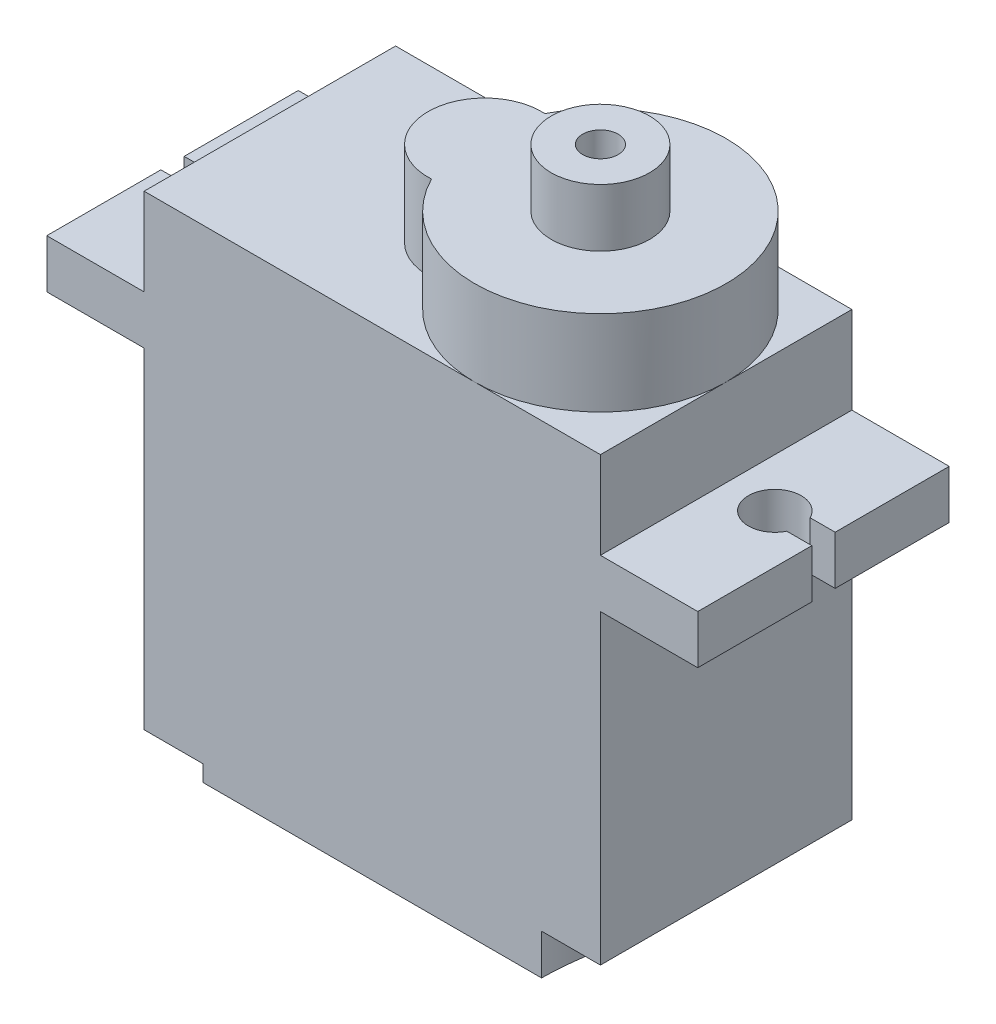
SolidWorks part; units mm, degrees
ref_plane "Alzado" through (0, 0, 0) normal (0, 0, 1) x (1, 0, 0)
ref_plane "Planta" through (0, 0, 0) normal (0, 1, 0) x (1, 0, 0)
ref_plane "Vista lateral" through (0, 0, 0) normal (1, 0, 0) x (0, 0, -1)
sketch "Croquis1" plane through (0, 0, 0) normal (0, 0, 1) x (1, 0, 0)
  line L0 (0, 11.9) -> (0, -11.9) construction
  line L4 (-11.25, -11.9) -> (-11.25, 11.9)
  line L5 (-11.25, 11.9) -> (11.25, 11.9)
  line L6 (-11.25, -11.9) -> (11.25, -11.9)
  line L7 (-16.05, 5.2) -> (-11.25, 5.2)
  line L8 (-16.05, 5.2) -> (-16.05, 7.6)
  line L9 (-16.05, 7.6) -> (-11.25, 7.6)
  line L10 (-11.25, 5.2) -> (-11.25, 7.6)
  line L11 (-16.05, 5.2) -> (-11.25, 7.6) construction
  line L12 (-16.05, 7.6) -> (-11.25, 5.2) construction
  line L14 (11.25, -11.9) -> (11.25, 11.9)
  line L16 (16.05, 7.6) -> (11.25, 7.6)
  line L17 (11.25, 5.2) -> (11.25, 7.6)
  line L18 (16.05, 5.2) -> (11.25, 5.2)
  line L19 (16.05, 5.2) -> (16.05, 7.6)
  point P0 (0, 0)
  point P2 (-11.25, 0)
  point P6 (-13.65, 6.4)
  dimension "D1" = 23.8
  dimension "D2" = 2.4
  dimension "D3" = 22.5
  dimension "D4" = 4.8
  dimension "D5" = 4.3
extrude "Saliente-Extruir1" add sketch "Croquis1" along normal mid plane 12.4 contours L9 L8 L7 L4 | L6 L14 L5 L4 | L18 L19 L16 L14 region at (0, 0, 0) region at (-13.65, 6.4, 0) region at (13.65, 6.4, 0)
sketch "Croquis2" plane through (0, 11.9, 0) normal (0, 1, 0) x (1, 0, 0)
  line L0 (-11.25, 6.2) -> (11.25, 6.2) construction
  line L1 (-11.25, -6.2) -> (11.25, -6.2) construction
  line L2 (11.25, -6.2) -> (11.25, 6.2) construction
  line L3 (-0.65, 0) -> (-3.45, 0) construction
  arc A0 (-0.4842, -2.7951) -> (-0.4842, 2.7951) centre (5.05, 0) ccw
  arc A1 (-0.4842, 2.7951) -> (-0.4842, -2.7951) centre (-0.65, 0) ccw
  dimension "D2" = 5.6
  dimension "D1" = 14.7
extrude "Saliente-Extruir2" add sketch "Croquis2" along normal blind 4.2
sketch "Croquis3" plane through (0, 7.6, 0) normal (0, 1, 0) x (1, 0, 0)
  line L0 (0, -6.2) -> (0, 6.2) construction
  line L1 (-11.25, -6.2) -> (5.05, -6.2) construction
  line L2 (-11.25, 6.2) -> (5.05, 6.2) construction
  line L3 (16.05, 0.575) -> (14.8159, 0.575)
  line L4 (16.05, -6.2) -> (16.05, 6.2) construction
  line L5 (16.05, -0.575) -> (14.8159, -0.575)
  line L6 (16.05, 0.575) -> (16.05, -0.575)
  line L7 (-16.05, 0.575) -> (-14.8159, 0.575)
  line L8 (-16.05, 0.575) -> (-16.05, -0.575)
  line L9 (-16.05, -0.575) -> (-14.8159, -0.575)
  arc A1 (14.8159, 0.575) -> (14.8159, -0.575) centre (13.65, 0) ccw
  arc A2 (-14.8159, 0.575) -> (-14.8159, -0.575) centre (-13.65, 0) cw
  point P16 (16.05, 0)
  point P18 (16.05, 0)
  dimension "D2" = 2.6
  dimension "D1" = 1.15
  dimension "D3" = 2.4
extrude "Cortar-Extruir1" cut sketch "Croquis3" against normal up to next
sketch "Croquis4" plane through (0, -11.9, 0) normal (0, -1, 0) x (1, 0, 0)
  line L0 (0, 6.2) -> (0, -6.2) construction
  line L1 (-11.25, 0) -> (11.25, 0) construction
  line L2 (-11.25, 3.3) -> (-11.25, 6.2)
  line L3 (-11.25, 6.2) -> (-8.35, 6.2)
  line L4 (-11.25, -6.2) -> (11.25, -6.2)
  line L5 (11.25, -6.2) -> (11.25, 6.2)
  line L6 (11.25, 6.2) -> (-11.25, 6.2)
  line L7 (-11.25, 6.2) -> (-11.25, -6.2)
  line L8 (-11.25, -6.2) -> (11.25, -6.2)
  line L9 (11.25, -6.2) -> (11.25, 6.2)
  line L10 (11.25, 6.2) -> (-11.25, 6.2)
  line L11 (-11.25, 6.2) -> (-11.25, -6.2)
  line L12 (-11.25, -3.3) -> (-11.25, -6.2)
  line L13 (-11.25, -6.2) -> (-8.35, -6.2)
  line L14 (11.25, 3.3) -> (11.25, 6.2)
  line L15 (11.25, 6.2) -> (8.35, 6.2)
  line L16 (11.25, -3.3) -> (11.25, -6.2)
  line L17 (11.25, -6.2) -> (8.35, -6.2)
  line L18 (8.35, 6.2) -> (8.35, -6.2)
  line L19 (9.75, -1.875) -> (11.25, -1.875)
  line L20 (9.75, -1.875) -> (9.75, 1.875)
  line L21 (9.75, 1.875) -> (11.25, 1.875)
  line L22 (11.25, -1.875) -> (11.25, 1.875)
  line L23 (9.75, -1.875) -> (11.25, 1.875) construction
  line L24 (9.75, 1.875) -> (11.25, -1.875) construction
  arc A0 (-8.35, 6.2) -> (-11.25, 3.3) centre (-11.25, 6.2) cw
  arc A1 (-8.35, -6.2) -> (-11.25, -3.3) centre (-11.25, -6.2) ccw
  arc A2 (8.35, 6.2) -> (11.25, 3.3) centre (11.25, 6.2) ccw
  arc A3 (8.35, -6.2) -> (11.25, -3.3) centre (11.25, -6.2) cw
  point P17 (10.5, 0)
  dimension "D2" = 2.9
  dimension "D3" = 3.75
  dimension "D4" = 1.5
  dimension "D1" = 0
extrude "Cortar-Extruir3" cut sketch "Croquis4" against normal blind 0.8 contours A0 L16 L4 | L17 A1 L11 region at (-10.0192, -11.9, 4.9692) region at (-10.0192, -11.9, -4.9692)
extrude "Cortar-Extruir4" cut sketch "Croquis4<5>" against normal blind 2 contours L16 A2 L9 | L21 L20 L19 A3 | A3 L17 region at (10.0192, -11.9, 4.9692) region at (10.0192, -11.9, -4.9692) region at (10.5, -11.9, 0)
sketch "Croquis4<5>" plane through (0, -11.9, 0) normal (0, -1, 0) x (1, 0, 0) same geometry as "Croquis4"
sketch "Croquis6" plane through (0, 0, -6.2) normal (0, 0, -1) x (-1, 0, 0)
  line L0 (-11.25, -9.9) -> (-8.35, -11.9)
  line L1 (-8.35, -11.9) -> (-11.25, -11.9)
  line L2 (-11.25, -11.9) -> (-11.25, -9.9)
extrude "Cortar-Extruir5" cut sketch "Croquis6" against normal through all
sketch "Croquis7" plane through (0, 16.1, 0) normal (0, 1, 0) x (1, 0, 0)
  circle A0 centre (5.05, 0) radius 2.425
  circle A1 centre (5.05, 0) radius 0.875
  dimension "D1" = 4.85
  dimension "D2" = 1.55
extrude "Saliente-Extruir4" add sketch "Croquis7" along normal blind 2.85
sketch "Sketch1" plane through (0, 18.95, 0) normal (0, 1, 0) x (1, 0, 0)
  circle A0 centre (5.05, 0) radius 3.5
  circle A1 centre (5.05, 0) radius 2.425
  circle M1 centre (5.05, 0) radius 2.425
extrude "Boss-Extrude1" [suppressed] add sketch "Sketch1" against normal blind 10 and the other way blind 2 contours A0 M1
sketch "Sketch2" [suppressed] plane through (0, 20.95, 0) normal (0, 1, 0) x (1, 0, 0)
  line L0 (5.5778, 3.46) -> (20.5403, 1.1775)
  line L1 (5.5787, -3.4598) -> (20.5406, -1.1733)
  line L2 (1.55, 0) -> (21.55, 0.0022) construction
  circle A0 centre (5.05, 0) radius 3.5
  arc A1 (20.5403, 1.1775) -> (20.5406, -1.1733) centre (20.3609, 0.0021) cw
  circle M5 centre (5.05, 0) radius 2.425
  circle M6 centre (5.05, 0) radius 3.5
  dimension "D1" = 20
extrude "Boss-Extrude2" [suppressed] add sketch "Sketch2" against normal blind 1 contours A0 L2 A1 L0 | L2 L1 A1 M6 | L2 A0 M6 M5 | L2 A0 M6 M5
